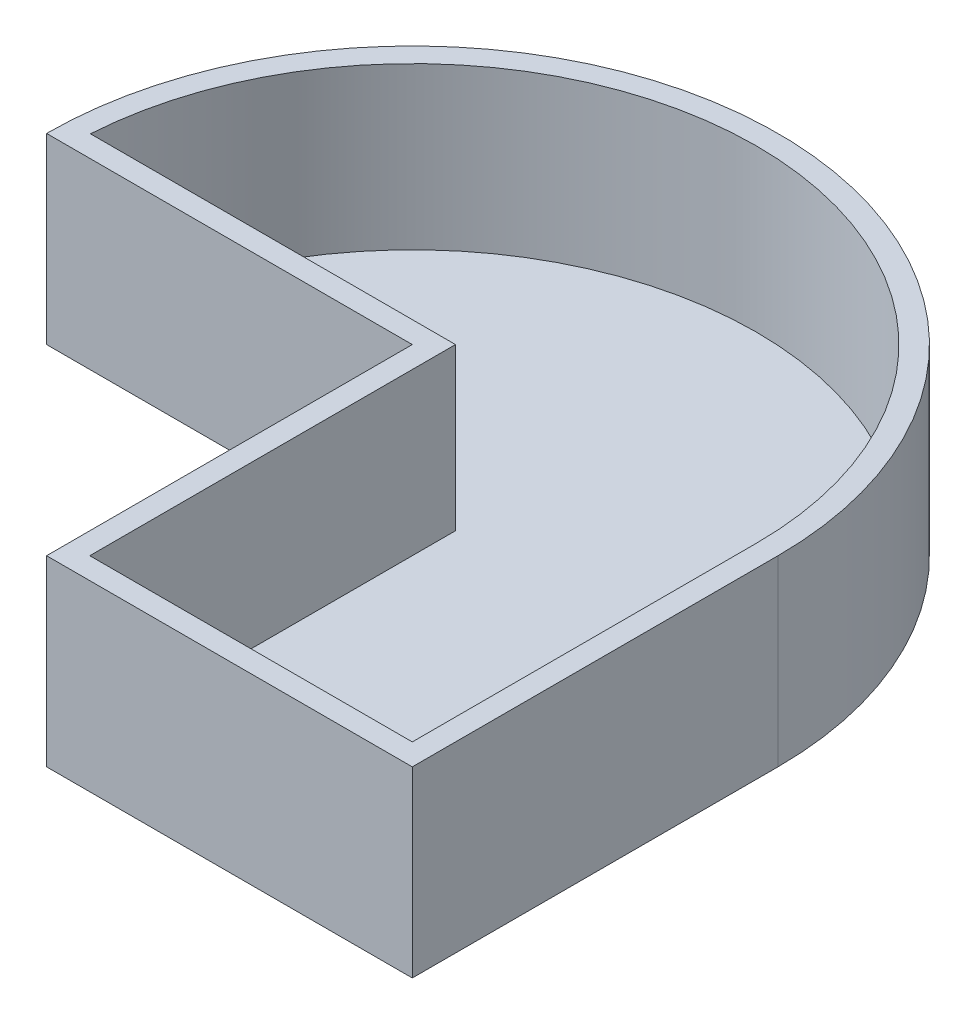
SolidWorks part; units mm, degrees
ref_plane "Front Plane" through (0, 0, 0) normal (0, 0, 1) x (1, 0, 0)
ref_plane "Top Plane" through (0, 0, 0) normal (0, 1, 0) x (1, 0, 0)
ref_plane "Right Plane" through (0, 0, 0) normal (1, 0, 0) x (0, 0, -1)
sketch "Sketch1" plane through (0, 0, 0) normal (0, 1, 0) x (1, 0, 0)
  line L0 (0, 0) -> (0, 50.8)
  line L1 (0, 0) -> (50.8, 0)
  line L2 (50.8, 0) -> (50.8, 50.8)
  line L3 (0, 50.8) -> (-50.8, 50.8)
  arc A0 (50.8, 50.8) -> (-50.8, 50.8) centre (0, 50.8) ccw
  dimension "D1" = 50.8
  dimension "D3" = 50.8
extrude "Boss-Extrude1" add sketch "Sketch1" along normal blind 25.4
sketch "Sketch2" plane through (0, 25.4, 0) normal (0, 1, 0) x (1, 0, 0)
  line L12 (3, 3) -> (47.8, 3)
  line L13 (47.8, 3) -> (47.8, 50.8)
  line L14 (-47.7058, 53.8) -> (3, 53.8)
  line L15 (3, 53.8) -> (3, 3)
  line L16 (3, 3) -> (47.8, 3)
  line L17 (47.8, 3) -> (47.8, 50.8)
  line L18 (-47.7058, 53.8) -> (3, 53.8)
  line L19 (3, 53.8) -> (3, 3)
  arc A3 (47.8, 50.8) -> (-47.7058, 53.8) centre (0, 50.8) ccw
  arc A4 (47.8, 50.8) -> (-47.7058, 53.8) centre (0, 50.8) ccw
  dimension "D1" = 3
extrude "Cut-Extrude1" cut sketch "Sketch2" against normal offset from surface (22.4 mm away) 3 up to face at (10.16, 0, -40.64)
